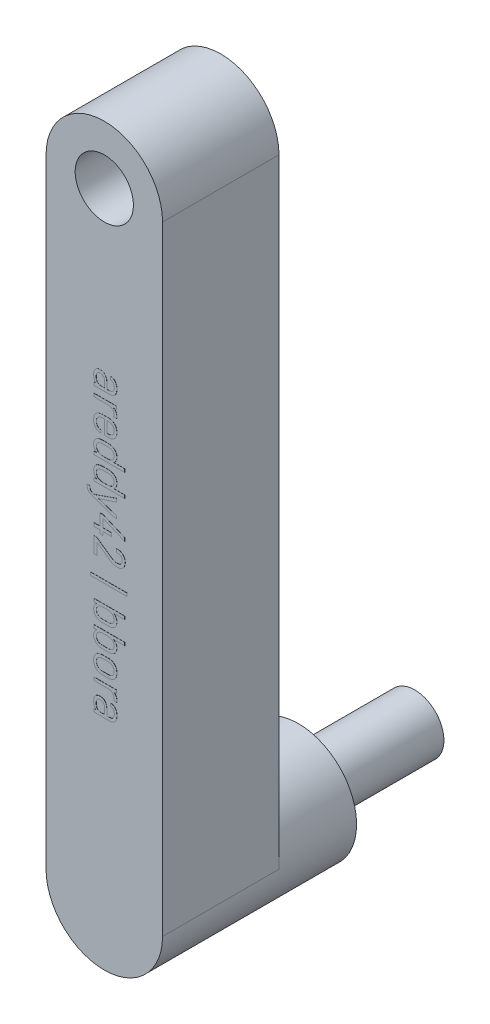
SolidWorks part; units mm, degrees
ref_plane "Front Plane" through (0, 0, 0) normal (0, 0, 1) x (1, 0, 0)
ref_plane "Top Plane" through (0, 0, 0) normal (0, 1, 0) x (1, 0, 0)
ref_plane "Right Plane" through (0, 0, 0) normal (1, 0, 0) x (0, 0, -1)
sketch "sketch1_link2" plane through (0, 0, 0) normal (0, 0, 1) x (1, 0, 0)
  circle A0 centre (0, 0) radius 20
  dimension "D1" = 40
extrude "Boss-Extrude1" add sketch "sketch1_link2" along normal mid plane 80 contours A0
sketch "sketch2_link2" plane through (0, 0, 40) normal (0, 0, 1) x (1, 0, 0)
  circle A0 centre (0, 0) radius 40
  dimension "D1" = 80
extrude "Boss-Extrude2" add sketch "sketch2_link2" along normal blind 53.3
sketch "sketch3_link2" plane through (0, 0, 93.3) normal (0, 0, 1) x (1, 0, 0)
  line L0 (-40, 0) -> (-40, 425)
  line L1 (40, 0) -> (40, 425)
  arc A0 (-40, 0) -> (40, 0) centre (0, 0) ccw
  arc A1 (-40, 425) -> (40, 425) centre (0, 425) cw
  circle A2 centre (0, 425) radius 20
  dimension "D1" = 40
  dimension "D3" = 40
  dimension "D2" = 425
extrude "Boss-Extrude3" add sketch "sketch3_link2" along normal blind 80
sketch "Sketch1" plane through (0, 0, 173.3) normal (0, 0, 1) x (1, 0, 0)
  line L0 (-7, 464.3827) -> (-7, -39.3827) construction
  line L1 (-40, 425) -> (-40, 0) construction
  arc A0 (40, 425) -> (-40, 425) centre (0, 425) ccw construction
  arc A1 (-40, 0) -> (40, 0) centre (0, 0) ccw construction
  text T0 "areddy42 | bbora" font "D-DIN" height in points 72
  dimension "D1" = 47
extrude "Boss-Extrude4" add sketch "Sketch1" along normal blind 0.1
